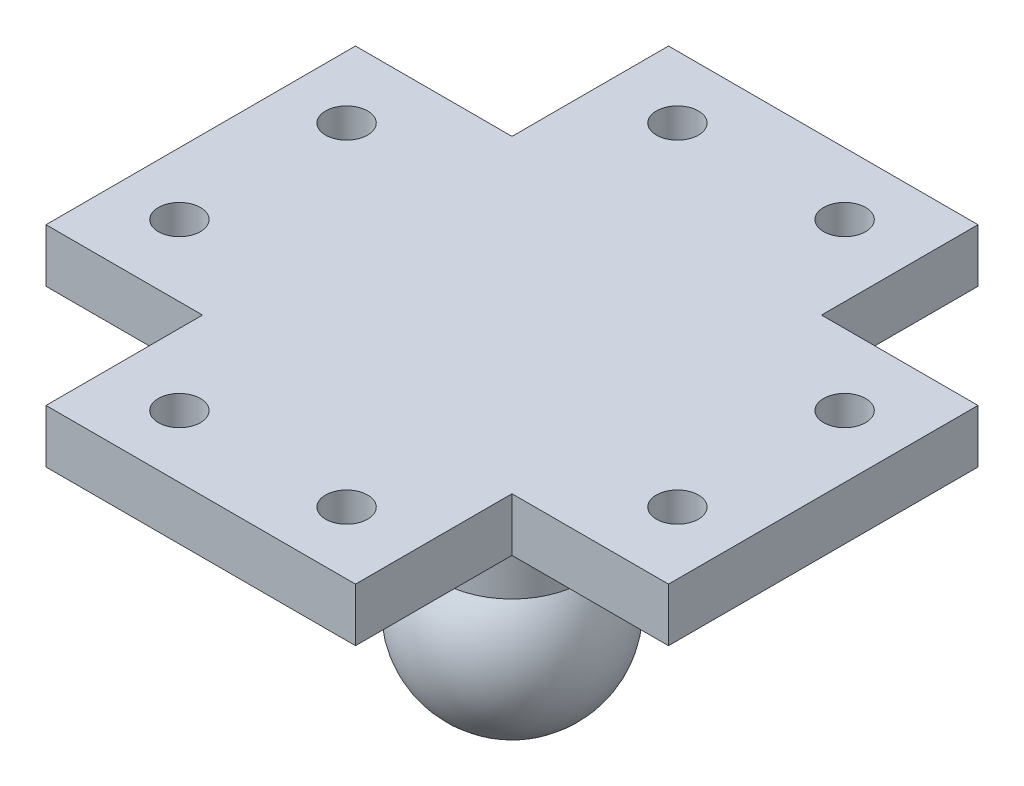
SolidWorks part; units mm, degrees
ref_plane "Front Plane" through (0, 0, 0) normal (0, 0, 1) x (1, 0, 0)
ref_plane "Top Plane" through (0, 0, 0) normal (0, 1, 0) x (1, 0, 0)
ref_plane "Right Plane" through (0, 0, 0) normal (1, 0, 0) x (0, 0, -1)
sketch "Sketch1" plane through (0, 0, 0) normal (0, 0, 1) x (1, 0, 0)
  line L0 (0, -6.604) -> (0, 6.604)
  line L1 (0, 6.604) -> (0, 14.3798)
  line L2 (-5.08, 14.3798) -> (0, 14.3798)
  line L3 (-5.08, 14.3798) -> (-5.08, 4.2198)
  arc A1 (-5.08, 4.2198) -> (0, -6.604) centre (0, 0) ccw
  point P5 (0, 9.2998)
  dimension "D1" = 6.604
  dimension "D2" = 5.08
  dimension "D3" = 10.16
revolve "Revolve3" add sketch "Sketch1" angle 360 about L0 region at (-2.7448, 3.9059, 0)
sketch "Sketch2" plane through (0, 14.3798, 0) normal (0, 1, 0) x (1, 0, 0)
  line L1 (-22.225, 11.049) -> (22.225, 11.049)
  line L2 (-22.225, 11.049) -> (-22.225, -11.049)
  line L3 (-22.225, -11.049) -> (22.225, -11.049)
  line L4 (22.225, 11.049) -> (22.225, -11.049)
  line L5 (-22.225, 11.049) -> (22.225, -11.049) construction
  line L6 (-22.225, -11.049) -> (22.225, 11.049) construction
  line L7 (11.049, -22.225) -> (-11.049, -22.225)
  line L8 (11.049, -22.225) -> (11.049, 22.225)
  line L9 (11.049, 22.225) -> (-11.049, 22.225)
  line L10 (-11.049, -22.225) -> (-11.049, 22.225)
  line L11 (11.049, -22.225) -> (-11.049, 22.225) construction
  line L12 (11.049, 22.225) -> (-11.049, -22.225) construction
  circle A0 centre (-17.78, -5.969) radius 1.5
  circle A1 centre (-17.78, 5.969) radius 1.5
  circle A2 centre (-5.969, 17.78) radius 1.5
  circle A3 centre (5.969, 17.78) radius 1.5
  circle A4 centre (17.78, 5.969) radius 1.5
  circle A5 centre (17.78, -5.969) radius 1.5
  circle A6 centre (5.969, -17.78) radius 1.5
  circle A7 centre (-5.969, -17.78) radius 1.5
  point P0 (0, 0)
  point P6 (0, 0)
  point P15 (0.7942, -24.9242)
  point P16 (0, 0)
  point P30 (0, 0)
  circle M9 centre (0, 0) radius 5.08
  dimension "D3" = 3
  dimension "D1" = 22.098
  dimension "D2" = 44.45
  dimension "D4" = 5.08
  dimension "D5" = 5.08
  dimension "D6" = 4.445
  dimension "D7" = 4
extrude "Boss-Extrude1" add sketch "Sketch2" along normal blind 3.81 contours L3 L10 L1 L2 | L10 L1 M9 | M9 | L10 L3 M9 | L10 L7 L8 L3 | L8 L3 L4 L1 | L8 L1 M9 | L3 L8 M9 | L10 L1 L8 L9 region at (-16.5676, 14.3798, 0) region at (0, 14.3798, -16.5676) region at (0, 14.3798, -10.7365) region at (16.5676, 14.3798, 0) region at (0, 14.3798, 16.5676) region at (0, 14.3798, 0)
fillet "Fillet1" radius 5.08 1 edges at (0, 14.3798, -5.08)
